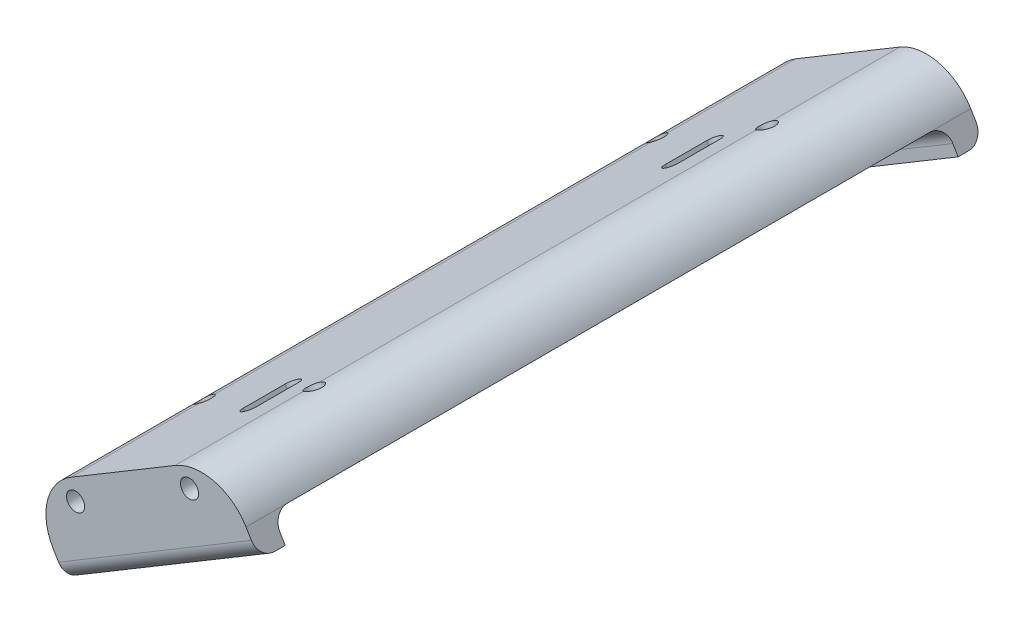
SolidWorks part; units mm, degrees
ref_plane "前视基准面" through (0, 0, 0) normal (0, 0, 1) x (1, 0, 0)
ref_plane "上视基准面" through (0, 0, 0) normal (0, 1, 0) x (1, 0, 0)
ref_plane "右视基准面" through (0, 0, 0) normal (1, 0, 0) x (0, 0, -1)
other "Configuration Table"
sketch "草图2" plane through (-32.0591, 54.9401, -3.7405) normal (0, 0, 1) x (1, 0, 0)
  line L0 (-9.4044, 34.5643) -> (-25.9417, 62.2117) construction
  line L1 (-31.4185, 21.3969) -> (-47.9555, 49.0437) construction
  line L2 (-17.6731, 48.388) -> (-39.687, 35.2203) construction
  line L3 (1.5178, 33.5919) -> (4.0845, 29.301)
  line L4 (-28.68, 41.8042) -> (-38.5, 58.2222) construction
  line L5 (-28.68, 41.8042) -> (-10.0573, 52.9434) construction
  line L6 (-10.0573, 52.9434) -> (25656.3635, -42856.6691) construction
  line L7 (-12.1974, 37.0406) -> (-32.2791, 25.0287)
  line L8 (-35.7277, 11.3135) -> (-33.1611, 7.0225)
  line L9 (-33.1611, 7.0225) -> (4.0845, 29.301)
  line L11 (0.2345, 35.7374) -> (-37.0111, 13.459) construction
  line L12 (1.5178, 33.5919) -> (-35.7277, 11.3135) construction
  circle A2 centre (-31.4185, 21.3969) radius 1.75
  circle A4 centre (-9.4044, 34.5643) radius 1.75
  circle A6 centre (-47.9555, 49.0437) radius 1.75
  circle A8 centre (-25.9417, 62.2117) radius 1.75
  arc A10 (-34.1465, 21.0497) -> (-28.7563, 22.0862) centre (-31.4185, 21.3969) ccw construction
  arc A11 (-11.271, 32.5448) -> (-7.8081, 36.8035) centre (-9.4044, 34.5643) ccw construction
  arc A12 (-10.5922, 33.2791) -> (-8.3886, 35.9893) centre (-9.4044, 34.5643) ccw
  arc A13 (-33.1545, 21.1759) -> (-29.7244, 21.8356) centre (-31.4185, 21.3969) ccw
  circle A14 centre (-9.4044, 34.5643) radius 1.75
  circle A15 centre (-31.4185, 21.3969) radius 1.75
  arc A16 (-32.2791, 25.0287) -> (-35.7277, 11.3135) centre (-27.1458, 16.4468) ccw
  arc A17 (-12.1974, 37.0406) -> (1.5178, 33.5919) centre (-7.0641, 28.4587) cw
  point P42 (-3.6155, 42.1739)
  dimension "D6" = 10
  dimension "D5" = 1
  dimension "D7" = 15
extrude "凸台-拉伸1" add sketch "草图2" along normal blind 140 contours A17 L7 A16 L8 L9 L3 A4 A2 region at (-50.1842, 79.0983, -3.7405)
sketch "草图3" plane through (16.5079, 9.8742, 0) normal (0.8582, 0.5133, 0) x (0, 0, -1)
  line L0 (-136.2595, 91.6552) -> (3.7405, 91.6552) construction
  line L1 (-1.2595, 91.6552) -> (-131.2595, 91.6552)
  line L2 (-1.2595, 91.6552) -> (-1.2595, 48.1336)
  line L3 (-1.2595, 48.1336) -> (-131.2595, 48.1336)
  line L4 (-131.2595, 91.6552) -> (-131.2595, 48.1336)
  line L5 (3.7405, 91.6552) -> (3.7405, 101.6552) construction
  line L6 (-136.2595, 101.6552) -> (-136.2595, 91.6552) construction
  dimension "D1" = 5
  dimension "D2" = 5
extrude "切除-拉伸1" cut sketch "草图3" against normal blind 140
fillet "圆角1" radius 3 4 edges at (-49.1641, 77.3928, 1.2595) (-49.1641, 77.3928, 131.2595) (-46.5974, 73.1018, 136.2595) (-46.5974, 73.1018, -3.7405)
ref_plane "基准面1" through (0, 0, 66.2595) normal (0, 0, -1) x (-1, 0, 0)
sketch "草图4" plane through (-47.0492, 78.6578, 0) normal (0.5133, -0.8582, 0) x (-0.8582, -0.5133, 0)
  arc A0 (-1.065, -62.1157) -> (-1.065, -59.2157) centre (-1.065, -60.6657) ccw
  arc A1 (-1.065, -59.2157) -> (-1.065, -62.1157) centre (-1.065, -60.6657) ccw
  arc A2 (-1.065, -61.9157) -> (-1.065, -59.4157) centre (-1.065, -60.6657) ccw
  arc A3 (-1.065, -59.4157) -> (-1.065, -61.9157) centre (-1.065, -60.6657) ccw
  arc A4 (-1.065, -61.9157) -> (-1.065, -59.4157) centre (-1.065, -60.6657) ccw construction
  arc A5 (-1.065, -59.4157) -> (-1.065, -61.9157) centre (-1.065, -60.6657) ccw construction
  arc A6 (34.935, -59.4157) -> (34.935, -61.9157) centre (34.935, -60.6657) ccw
  arc A7 (34.935, -61.9157) -> (34.935, -59.4157) centre (34.935, -60.6657) ccw
  arc A8 (34.935, -59.4157) -> (34.935, -61.9157) centre (34.935, -60.6657) ccw construction
  arc A9 (34.935, -61.9157) -> (34.935, -59.4157) centre (34.935, -60.6657) ccw construction
  arc A10 (34.935, -97.9157) -> (34.935, -95.4157) centre (34.935, -96.6657) ccw
  arc A11 (34.935, -95.4157) -> (34.935, -97.9157) centre (34.935, -96.6657) ccw
  arc A12 (34.935, -97.9157) -> (34.935, -95.4157) centre (34.935, -96.6657) ccw construction
  arc A13 (34.935, -95.4157) -> (34.935, -97.9157) centre (34.935, -96.6657) ccw construction
  arc A14 (-1.065, -97.9157) -> (-1.065, -95.4157) centre (-1.065, -96.6657) ccw
  arc A15 (-1.065, -95.4157) -> (-1.065, -97.9157) centre (-1.065, -96.6657) ccw
  arc A16 (-1.065, -97.9157) -> (-1.065, -95.4157) centre (-1.065, -96.6657) ccw construction
  arc A17 (-1.065, -95.4157) -> (-1.065, -97.9157) centre (-1.065, -96.6657) ccw construction
  arc A18 (34.935, -59.2157) -> (34.935, -62.1157) centre (34.935, -60.6657) ccw
  arc A19 (34.935, -62.1157) -> (34.935, -59.2157) centre (34.935, -60.6657) ccw
  arc A20 (34.935, -98.1157) -> (34.935, -95.2157) centre (34.935, -96.6657) ccw
  arc A21 (34.935, -95.2157) -> (34.935, -98.1157) centre (34.935, -96.6657) ccw
  arc A22 (-1.065, -98.1157) -> (-1.065, -95.2157) centre (-1.065, -96.6657) ccw
  arc A23 (-1.065, -95.2157) -> (-1.065, -98.1157) centre (-1.065, -96.6657) ccw
  dimension "D1" = 0
  dimension "D2" = 0
  dimension "D3" = 0
  dimension "D4" = 0
  dimension "D5" = 0.2
extrude "切除-拉伸2" cut sketch "草图4" against normal up to surface (5 mm away) contours A22 A23 | A20 A21 | A0 A1 | A18 A19 rebuild error yes up to face at (-46.5974, 73.1018, 0.2595)
sketch "草图6" plane through (-44.4826, 74.3668, 0) normal (0.5133, -0.8582, 0) x (0.8582, 0.5133, 0)
  line L0 (-24.1643, 133.2595) -> (-24.1643, 131.2595) construction
  line L1 (19.2357, 133.2595) -> (19.2357, 131.2595) construction
  line L2 (-15.8739, 66.2595) -> (15.8739, 66.2595) construction
  circle A0 centre (-14.8175, 110) radius 1.65
  circle A1 centre (9.8857, 110) radius 1.65
  circle A2 centre (9.8857, 22.519) radius 1.65
  circle A3 centre (-14.8175, 22.519) radius 1.65
  dimension "D1" = 9.3468
  dimension "D2" = 9.35
extrude "切除-拉伸3" cut sketch "草图6" against normal through all
sketch "草图7" plane through (-44.4826, 74.3668, 0) normal (0.5133, -0.8582, 0) x (0.8582, 0.5133, 0)
  line L0 (19.2357, 128.2595) -> (19.2357, 4.2595) construction
  line L1 (0.565, 11.8657) -> (0.565, 129.8657) construction
  line L2 (19.2357, 128.2595) -> (19.2357, 4.2595)
  line L3 (0.565, 11.8657) -> (0.565, 129.8657)
  line L4 (2.065, 34.1185) -> (2.065, 26.1185) construction
  line L5 (3.565, 34.1185) -> (3.565, 26.1185)
  line L6 (0.565, 34.1185) -> (0.565, 26.1185)
  line L7 (0.565, 70.8657) -> (16.3298, 70.8657) construction
  line L8 (2.065, 107.6129) -> (2.065, 115.6129) construction
  line L9 (3.565, 107.6129) -> (3.565, 115.6129)
  line L10 (0.565, 107.6129) -> (0.565, 115.6129)
  arc A0 (3.565, 34.1185) -> (0.565, 34.1185) centre (2.065, 34.1185) ccw
  circle A1 centre (-4.585, 110) radius 1.65
  circle A2 centre (-4.585, 110) radius 1.65 construction
  circle A3 centre (-4.585, 31.7314) radius 1.65
  circle A4 centre (-4.585, 31.7314) radius 1.65 construction
  arc A5 (0.565, 26.1185) -> (3.565, 26.1185) centre (2.065, 26.1185) ccw
  arc A6 (3.565, 107.6129) -> (0.565, 107.6129) centre (2.065, 107.6129) cw
  arc A7 (0.565, 115.6129) -> (3.565, 115.6129) centre (2.065, 115.6129) cw
  point P12 (2.065, 30.1185)
  point P21 (2.065, 111.6129)
  dimension "D3" = 3
  dimension "D4" = 8
  dimension "D5" = 0
  dimension "D1" = 0
  dimension "D2" = 0
extrude "切除-拉伸5" cut sketch "草图7" against normal through all contours L3 A5 L5 A0 | L9 A7 L10 A6 region at (-42.7104, 75.4269, 30.1185)
